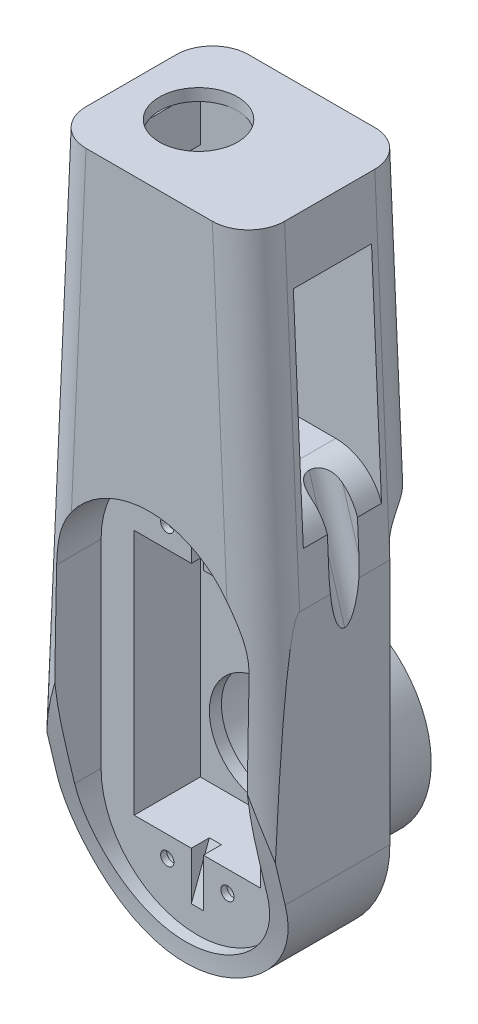
SolidWorks part; units mm, degrees
ref_plane "Front Plane" through (0, 0, 0) normal (0, 0, 1) x (1, 0, 0)
ref_plane "Top Plane" through (0, 0, 0) normal (0, 1, 0) x (1, 0, 0)
ref_plane "Right Plane" through (0, 0, 0) normal (1, 0, 0) x (0, 0, -1)
sketch "Sketch1" plane through (0, 0, 0) normal (0, 0, 1) x (1, 0, 0)
  line L5 (-19, -60) -> (19, -60)
  line L6 (-19, -60) -> (-19, 60)
  line L7 (-19, 60) -> (19, 60)
  line L8 (19, -60) -> (19, 60)
  line L9 (-19, -60) -> (19, 60) construction
  line L10 (-19, 60) -> (19, -60) construction
  line L11 (-10.5, -45) -> (10.5, -45)
  line L12 (-10.5, -45) -> (-10.5, -4)
  line L13 (-10.5, -4) -> (10.5, -4)
  line L14 (10.5, -45) -> (10.5, -4)
  line L15 (-10.5, -45) -> (10.5, -4) construction
  line L16 (-10.5, -4) -> (10.5, -45) construction
  point P0 (0, 0)
  point P6 (0, -24.5)
  dimension "D1" = 21
  dimension "D2" = 41
  dimension "D3" = 8.5
  dimension "D4" = 120
  dimension "D5" = 15
extrude "Boss-Extrude1" add sketch "Sketch1" along normal blind 11
ref_plane "Plane1" through (0, 0, 10) normal (0, 0, 1) x (1, 0, 0)
sketch "Sketch3" plane through (0, 0, 10) normal (0, 0, 1) x (1, 0, 0)
  line L0 (10.5, -4) -> (-10.5, -4) construction
  circle A0 centre (-5, -0.5) radius 1.3
  circle A1 centre (5, -0.5) radius 1.3
  circle A2 centre (5, -48.5) radius 1.3
  circle A3 centre (-5, -48.5) radius 1.3
  dimension "D1" = 2.6
  dimension "D2" = 5
  dimension "D3" = 3.5
  dimension "D4" = 2
  dimension "D5" = 2
extrude "Cut-Extrude1" cut sketch "Sketch3" against normal blind 8
fillet "Fillet3" radius 19 2 edges at (19, -60, 5.5) (-19, -60, 5.5)
sketch "Sketch4" plane through (0, 0, 11) normal (0, 0, 1) x (1, 0, 0)
  line L0 (16, -41) -> (16, 57)
  line L1 (16, 57) -> (-16, 57)
  line L2 (-16, 57) -> (-16, -41)
  line L3 (19, -41) -> (19, 60)
  line L4 (19, 60) -> (-19, 60)
  line L5 (-19, 60) -> (-19, -41)
  line L6 (19, -41) -> (19, 60)
  line L7 (19, 60) -> (-19, 60)
  line L8 (-19, 60) -> (-19, -41)
  arc A0 (-16, -41) -> (0, -57) centre (0, -41) ccw
  arc A1 (0, -57) -> (16, -41) centre (0, -41) ccw
  arc A2 (-19, -41) -> (0, -60) centre (0, -41) ccw
  arc A3 (0, -60) -> (19, -41) centre (0, -41) ccw
  arc A4 (-19, -41) -> (0, -60) centre (0, -41) ccw
  arc A5 (0, -60) -> (19, -41) centre (0, -41) ccw
  dimension "D1" = 0
  dimension "D2" = 3
extrude "Boss-Extrude2" add sketch "Sketch4" along normal blind 8
sketch "Sketch6" plane through (0, 0, 0) normal (1, 0, 0) x (0, 0, -1)
  line L7 (-13, -60) -> (-17, -35)
  line L8 (-17, -35) -> (-19, -20)
  line L9 (-19, -41) -> (-19, 60) construction
  line L10 (-19, -20) -> (-19, -60)
  line L11 (-19, -41) -> (-19, -60) construction
  line L12 (-19, -60) -> (-13, -60)
  line L13 (-11, -60) -> (0, -60) construction
  spline S0 degree 3 poles (-19, -20) (-18.8828, -33.6175) (-12.1748, -46.2563) (-13, -60) knots 0 0 0 0 1 1 1 1
  dimension "D1" = 6
  dimension "D2" = 25
  dimension "D3" = 15
  dimension "D4" = 2
extrude "Cut-Extrude2" cut sketch "Sketch6" against normal through all both and the other way through all contours L8 L7 | L10 L12 L7 L8 region at (0, -47.6101, 16.9935) region at (0, -47.9061, 14.5246)
sketch "Sketch7" plane through (0, 0, 11) normal (0, 0, 1) x (1, 0, 0)
  line L0 (16, -20) -> (16, 57) construction
  line L1 (16, 8) -> (-16, 8)
  line L2 (16, 8) -> (16, 57)
  line L3 (16, 57) -> (-16, 57)
  line L4 (-16, 8) -> (-16, 57)
  dimension "D1" = 49
extrude "Boss-Extrude4" add sketch "Sketch7" along normal up to surface (8 mm away) up to face at (0, 19.25, 19)
sketch "Sketch8" plane through (0, 0, 0) normal (0, 0, -1) x (-1, 0, 0)
  line L0 (-19, 60) -> (19, 60)
  line L1 (19, 60) -> (19, -6.3108)
  line L2 (19, 60) -> (19, -41) construction
  line L3 (-19, 60) -> (-19, -7)
  line L4 (-19, -41) -> (-19, 60) construction
  line L7 (19, 8) -> (-19, 8)
  arc A0 (19, -6.3108) -> (-19, -7) centre (0.25, -20.4388) ccw
  line M2 (-19, 60) -> (-19, -41)
  line M6 (19, 60) -> (-19, 60)
  dimension "D1" = 23.4769
  dimension "D2" = 67
  dimension "D3" = 19.25
  dimension "D4" = 52
extrude "Boss-Extrude5" add sketch "Sketch8" along normal blind 8 contours L7 L1 M6 M2 region at (0, 34, 0)
sketch "Sketch24" plane through (0, 0, 0) normal (0, 0, -1) x (-1, 0, 0)
  line L0 (10.5, -45) -> (-10.5, -45) construction
  line L3 (-19, 8) -> (-19, -41)
  line L4 (19, -41) -> (19, 8)
  line L5 (19, 8) -> (-19, 8)
  line L6 (-19, 8) -> (-19, -41)
  line L7 (19, -41) -> (19, 8)
  line L10 (19, 8) -> (-19, 8)
  circle A0 centre (0, -34.75) radius 9
  arc A2 (-19, -41) -> (0, -60) centre (0, -41) ccw
  arc A3 (0, -60) -> (19, -41) centre (0, -41) ccw
  arc A4 (-19, -41) -> (0, -60) centre (0, -41) ccw
  arc A5 (0, -60) -> (19, -41) centre (0, -41) ccw
  dimension "D2" = 18
  dimension "D3" = 10.25
  dimension "D1" = 0
extrude "Boss-Extrude6" add sketch "Sketch24" along normal blind 2
fillet "Fillet4" radius 16 2 edges at (-16, 8, 15) (16, 8, 15)
sketch "Sketch26" plane through (0, 60, 0) normal (0, 1, 0) x (1, 0, 0)
  line L4 (19, -19) -> (19, 8)
  line L5 (19, 8) -> (-19, 8)
  line L6 (-19, 8) -> (-19, -19)
  line L7 (-19, -19) -> (19, -19)
  line L8 (19, -19) -> (19, 8)
  line L9 (19, 8) -> (-19, 8)
  line L10 (-19, 8) -> (-19, -19)
  line L11 (-19, -19) -> (19, -19)
  dimension "D1" = 0
extrude "Cut-Extrude4" cut sketch "Sketch26" against normal blind 5
sketch "Sketch27" plane through (19, 0, 0) normal (1, 0, 0) x (0, 0, -1)
  line L0 (-19, 55) -> (8, 55) construction
  line L1 (-12, 45) -> (1, 45)
  line L2 (-12, 45) -> (-12, 14)
  line L3 (-12, 14) -> (1, 14)
  line L4 (1, 45) -> (1, 14)
  line L5 (-19, -20) -> (-19, 55) construction
  dimension "D1" = 10
  dimension "D2" = 31
  dimension "D3" = 13
  dimension "D4" = 7
extrude "Cut-Extrude5" cut sketch "Sketch27" against normal through all
sketch "Sketch29" plane through (0, 45, 0) normal (0, -1, 0) x (1, 0, 0)
  line L0 (-19, 12) -> (19, 12) construction
  line L1 (11.5, 12) -> (-11.5, 12)
  line L2 (11.5, 12) -> (11.5, -1)
  line L3 (11.5, -1) -> (-11.5, -1)
  line L4 (-11.5, 12) -> (-11.5, -1)
  line L5 (-19, -1) -> (19, -1) construction
  line L6 (19, -1) -> (19, 12) construction
  dimension "D1" = 23
  dimension "D2" = 7.5
extrude "Cut-Extrude7" cut sketch "Sketch29" against normal blind 8
sketch "Sketch28" plane through (0, 55, 0) normal (0, 1, 0) x (1, 0, 0)
  line L0 (-19, 8) -> (-19, -19) construction
  line L1 (19, 8) -> (-19, 8) construction
  circle A0 centre (-5.3, -5.5) radius 6.5
  dimension "D1" = 13
  dimension "D2" = 13.7
  dimension "D3" = 13.5
extrude "Cut-Extrude8" cut sketch "Sketch28" against normal blind 2 contours A0
sketch "Sketch30" plane through (0, 14, 0) normal (0, 1, 0) x (1, 0, 0)
  line L0 (-19, -12) -> (-19, 1) construction
  line L1 (-19, -3) -> (-13, -3)
  line L2 (-19, -3) -> (-19, -8)
  line L3 (-19, -8) -> (-13, -8)
  line L4 (-13, -3) -> (-13, -8)
  line L5 (19, -12) -> (19, 1) construction
  line L6 (19, -3) -> (13, -3)
  line L7 (19, -3) -> (19, -8)
  line L8 (19, -8) -> (13, -8)
  line L9 (13, -3) -> (13, -8)
  line L10 (-19, 8) -> (19, 8) construction
  dimension "D1" = 5
  dimension "D2" = 5
  dimension "D3" = 6
  dimension "D4" = 6
  dimension "D5" = 11
  dimension "D6" = 11
extrude "Cut-Extrude9" cut sketch "Sketch30" against normal blind 20
chamfer "Chamfer3" distance 20 distance2 6 2 edges at (13, -6, 5.5) (-13, -6, 5.5) first distance on face at (13, 4, 5.5) first distance on face at (-13, 4, 5.5)
fillet "Fillet6" radius 8 2 edges at (-19, 14, 1) (19, 14, 1)
fillet "Fillet7" radius 6 1 edges at (0, 8, -2)
fillet "Fillet9" [suppressed] radius 6
fillet "Fillet10" radius 2.5 4 edges at (16.0414, 3.8621, 3) (16.0414, 3.8621, 8) (-16.0414, 3.8621, 3) (-16.0414, 3.8621, 8)
sketch "Sketch31" plane through (0, 0, 11) normal (0, 0, 1) x (1, 0, 0)
  line L0 (10.5, -4) -> (-10.5, -4) construction
  circle A0 centre (-5, -0.5) radius 1.1
  circle A1 centre (5, -0.5) radius 1.1
  circle A2 centre (5, -48.5) radius 1.1
  circle A3 centre (-5, -48.5) radius 1.1
  dimension "D1" = 2.2
  dimension "D2" = 3.5
  dimension "D3" = 5
  dimension "D4" = 2
  dimension "D5" = 2
extrude "Cut-Extrude10" cut sketch "Sketch31" against normal blind 8
sketch "Sketch32" plane through (0, 45, 0) normal (0, -1, 0) x (1, 0, 0)
  line L0 (11.5, 5.5) -> (7.2313, 5.5) construction
  line L1 (11.5, -1) -> (11.5, 12) construction
  circle A0 centre (13.8, 5.5) radius 1.1
  circle A1 centre (-13.8, 5.5) radius 1.1
  dimension "D1" = 2.2
  dimension "D2" = 2.2
  dimension "D3" = 27.6
  dimension "D4" = 2.3
extrude "Cut-Extrude11" cut sketch "Sketch32" against normal blind 8
sketch "Sketch34" plane through (0, 0, 19) normal (0, 0, 1) x (1, 0, 0)
  line L0 (16.5, 55) -> (19, 0)
  line L1 (-19, 55) -> (19, 55) construction
  line L2 (19, -20) -> (19, 55) construction
  line L3 (19, 0) -> (19, 55)
  line L4 (19, 55) -> (16.5, 55)
  line L5 (-16.5, 55) -> (-19, 0)
  line L6 (-19, 55) -> (-19, -20) construction
  line L7 (-19, 0) -> (-19, 55)
  line L8 (-19, 55) -> (-16.5, 55)
  dimension "D1" = 2.5
  dimension "D2" = 2.5
  dimension "D3" = 55
  dimension "D4" = 55
extrude "Cut-Extrude13" cut sketch "Sketch34" against normal through all
fillet "Fillet11" radius 6 4 edges at (-17.5682, 31.5, -8) (-17.75, 27.5, 19) (17.5682, 31.5, -8) (17.75, 27.5, 19)
sketch "Sketch35" plane through (0, 0, -2) normal (0, 0, -1) x (-1, 0, 0)
  circle A0 centre (0, -34.75) radius 12.975
  circle A1 centre (0, -34.75) radius 16.875
  dimension "D1" = 3.9
  dimension "D2" = 25.95
extrude "Boss-Extrude7" add sketch "Sketch35" along normal blind 9
sketch "Sketch36" plane through (0, 0, 0) normal (1, 0, 0) x (0, 0, -1)
  line L0 (-11, -45) -> (-11, -53)
  line L1 (-11, -53) -> (-8, -45)
  line L2 (-8, -45) -> (-11, -45)
  line L3 (-11, -4) -> (-11, 4)
  line L4 (0, -45) -> (0, -4)
  line L5 (0, -4) -> (-11, -4)
  line L6 (-11, -4) -> (-11, -45)
  line L7 (-11, -45) -> (0, -45)
  line L8 (0, -45) -> (0, -4)
  line L9 (0, -4) -> (-11, -4)
  line L10 (-11, -4) -> (-11, -45)
  line L11 (-11, -45) -> (0, -45)
  line L12 (-11, 4) -> (-8, -4)
  line L13 (-8, -4) -> (-11, -4)
  dimension "D2" = 8
  dimension "D3" = 3
  dimension "D4" = 8
  dimension "D5" = 3
  dimension "D1" = 0
extrude "Cut-Extrude14" cut sketch "Sketch36" against normal mid plane 2 contours L0 L1 L2 | L3 L12 L13
